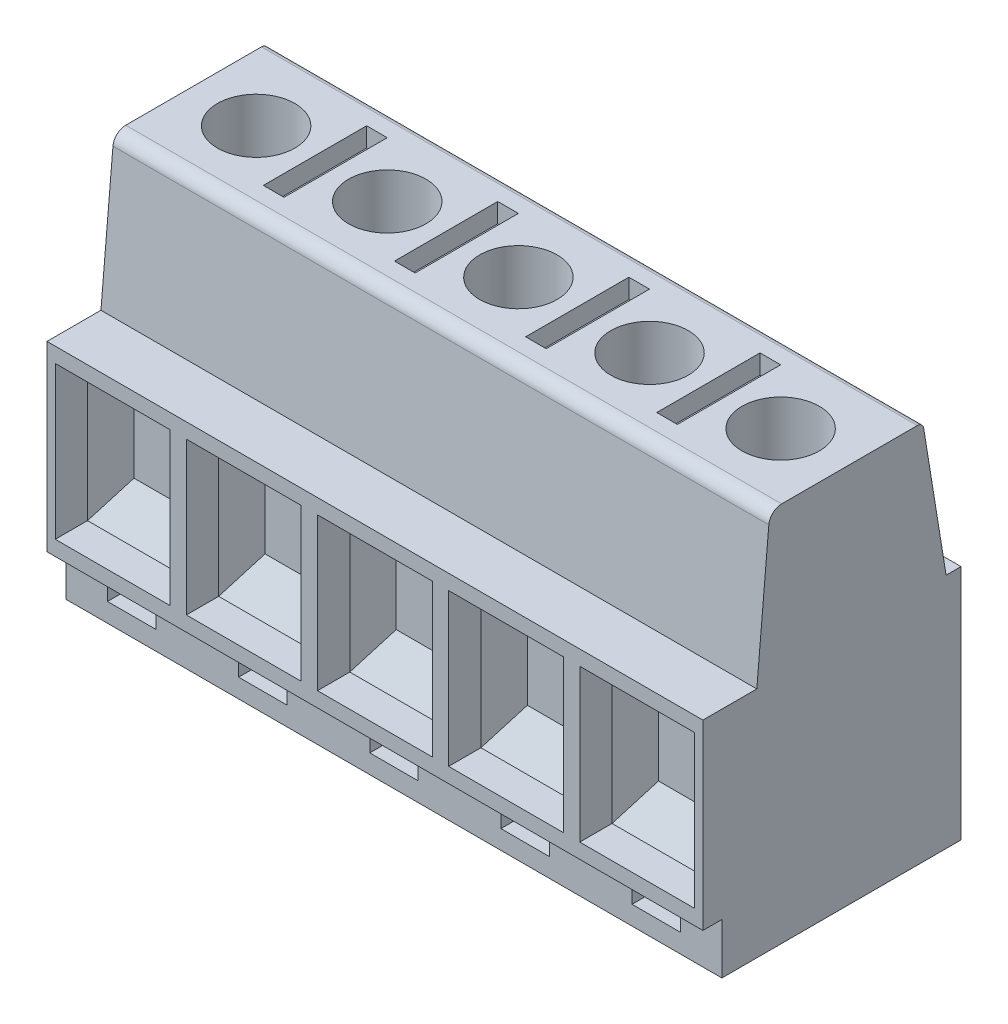
SolidWorks part; units mm, degrees
ref_plane "Front Plane" through (0, 0, 0) normal (0, 0, 1) x (1, 0, 0)
ref_plane "Top Plane" through (0, 0, 0) normal (0, 1, 0) x (1, 0, 0)
ref_plane "Right Plane" through (0, 0, 0) normal (1, 0, 0) x (0, 0, -1)
sketch "Sketch1" plane through (0, 0, 0) normal (1, 0, 0) x (0, 0, -1)
  line L0 (9.6447, 33.3244) -> (29.6447, 33.3244) construction
  line L1 (9.6692, 32.9692) -> (9.6692, 47.0868)
  line L2 (9.6692, 47.0868) -> (13.8475, 47.0868)
  line L3 (13.8475, 47.0868) -> (14.8593, 58.5419)
  line L4 (14.8593, 58.5419) -> (26.709, 58.5419)
  line L5 (26.709, 58.5419) -> (28.5149, 47.3865)
  line L6 (28.5149, 47.3865) -> (29.6692, 47.3865)
  line L7 (29.6692, 47.3865) -> (29.6692, 29.0419)
  line L8 (29.6692, 29.0419) -> (11.1423, 29.0419)
  line L9 (11.1423, 29.0419) -> (11.1423, 32.9692)
  line L10 (11.1423, 32.9692) -> (9.6692, 32.9692)
  line L11 (68.0457, 60.9618) -> (149.3457, 60.9618) construction
  line L12 (139.8559, 49.112) -> (148.7559, 49.112) construction
  line L13 (139.8559, 49.112) -> (139.8559, 37.312) construction
  line L14 (204.1416, 49.112) -> (206.6416, 49.112) construction
  line L15 (208.5587, 45.7504) -> (208.5587, 39.4578) construction
  line L16 (208.5587, 42.6041) -> (206.6416, 42.6041) construction
  line L17 (121.2763, 41.7533) -> (126.7736, 41.7533) construction
  line L18 (217.6919, 61.8593) -> (217.6919, 56.1569) construction
  line L19 (142.8406, 99.3741) -> (145.9297, 99.3741) construction
  line L20 (211.5813, 61.8593) -> (211.5813, 60.3558) construction
  line L21 (118.1896, 87.8673) -> (119.7969, 87.8673) construction
  line L22 (118.1896, 87.8673) -> (118.1896, 95.8627) construction
  line L23 (118.1896, 95.8627) -> (119.7969, 95.8627) construction
  line L24 (119.7969, 87.8673) -> (119.7969, 95.8627) construction
  line L25 (170.4098, 32.3653) -> (173.8098, 32.3653) construction
  line L26 (173.8098, 32.3653) -> (175.1098, 32.3653) construction
  line L27 (175.1098, 32.3653) -> (178.3098, 32.3653) construction
  line L28 (178.3098, 32.3653) -> (179.6098, 32.3653) construction
  line L29 (179.6098, 32.3653) -> (183.0098, 32.3653) construction
  line L30 (183.0098, 32.3653) -> (184.3098, 32.3653) construction
  line L31 (142.4541, 34.5696) -> (146.1866, 34.5696) construction
  line L32 (146.1866, 34.5696) -> (142.4541, 34.5696) construction
  line L33 (142.4541, 34.5696) -> (142.4541, 33.584) construction
  circle A0 centre (134.2519, 91.3377) radius 3.0186 construction
  dimension "D1" = 20
  dimension "D2" = 20
  dimension "D3" = 29.5
  dimension "D4" = 9.6692
  dimension "D5" = 11.1423
  dimension "D6" = 13.8475
  dimension "D7" = 14.8593
  dimension "D8" = 26.709
  dimension "D9" = 28.5149
  dimension "D10" = 29.0419
  dimension "D11" = 32.9692
  dimension "D12" = 33.3244
  dimension "D13" = 47.0868
  dimension "D14" = 47.3865
  dimension "D15" = 81.3
  dimension "D16" = 8.9
  dimension "D17" = 11.8
  dimension "D18" = 2.5
  dimension "D19" = 1.6073
  dimension "D20" = 7.9954
  dimension "D21" = 3.4
  dimension "D22" = 1.3
  dimension "D23" = 3.2
  dimension "D24" = 1.3
  dimension "D25" = 3.4
  dimension "D26" = 1.3
extrude "Boss-Extrude1" add sketch "Sketch1" along normal blind 10.16
sketch "Sketch2" plane through (0, 0, -9.6692) normal (0, 0, 1) x (1, 0, 0)
  line L0 (0, 47.0868) -> (0, 32.9692) construction
  line L1 (0.63, 34.128) -> (9.53, 34.128)
  line L2 (0.63, 34.128) -> (0.63, 45.928)
  line L3 (0.63, 45.928) -> (9.53, 45.928)
  line L4 (9.53, 34.128) -> (9.53, 45.928)
  line L5 (0.63, 34.128) -> (9.53, 45.928) construction
  line L6 (0.63, 45.928) -> (9.53, 34.128) construction
  line L7 (10.16, 47.0868) -> (0, 47.0868) construction
  point P0 (5.08, 40.028)
  point P5 (0, 0)
  point P8 (0, 40.028)
  point P9 (0, 0)
  point P12 (5.08, 47.0868)
  point P13 (9.3089, 45.6013)
  dimension "D1" = 8.9
  dimension "D2" = 11.8
extrude "Cut-Extrude1" cut sketch "Sketch2" against normal blind 2.5
sketch "Sketch3" plane through (0, 0, -12.1692) normal (0, 0, 1) x (1, 0, 0)
  line L4 (9.53, 34.128) -> (9.53, 45.928)
  line L5 (9.53, 45.928) -> (0.63, 45.928)
  line L6 (0.63, 45.928) -> (0.63, 34.128)
  line L7 (0.63, 34.128) -> (9.53, 34.128)
  line L8 (9.53, 34.128) -> (9.53, 45.928)
  line L9 (9.53, 45.928) -> (0.63, 45.928)
  line L10 (0.63, 45.928) -> (0.63, 34.128)
  line L11 (0.63, 34.128) -> (9.53, 34.128)
  dimension "D1" = 0
ref_plane "Plane1" through (0, 0, -14.0692) normal (0, 0, 1) x (1, 0, 0)
sketch "Sketch4" plane through (0, 0, -14.0692) normal (0, 0, 1) x (1, 0, 0)
  line L0 (9.53, 45.928) -> (0.63, 45.928) construction
  line L1 (2.33, 36.878) -> (7.83, 36.878)
  line L2 (2.33, 36.878) -> (2.33, 43.178)
  line L3 (2.33, 43.178) -> (7.83, 43.178)
  line L4 (7.83, 36.878) -> (7.83, 43.178)
  line L5 (2.33, 36.878) -> (7.83, 43.178) construction
  line L6 (2.33, 43.178) -> (7.83, 36.878) construction
  line L7 (0.63, 45.928) -> (0.63, 34.128) construction
  point P0 (5.08, 40.028)
  point P5 (0, 0)
  point P8 (5.08, 45.928)
  point P9 (0, 0)
  point P12 (0.63, 40.028)
  dimension "D1" = 6.3
  dimension "D2" = 5.5
loft "Cut-Loft1" cut profiles "Sketch3", "Sketch4" connector at (0.63, 45.928, -12.1692) connector at (2.33, 43.178, -14.0692)
sketch "Sketch5" plane through (0, 58.5419, 0) normal (0, 1, 0) x (1, 0, 0)
  line L0 (10.16, 26.709) -> (10.16, 14.8593) construction
  line L1 (10.16, 29.6692) -> (0, 29.6692) construction
  circle A0 centre (5.08, 20.7842) radius 3
  point P2 (0, 0)
  point P5 (10.16, 20.7842)
  point P6 (0, 0)
  point P9 (5.08, 29.6692)
  dimension "D1" = 6
extrude "Cut-Extrude2" cut sketch "Sketch5" against normal blind 5.7
sketch "Sketch7" plane through (0, 29.0419, 0) normal (0, -1, 0) x (1, 0, 0)
  line L0 (10.16, -11.1423) -> (0, -11.1423) construction
  line L1 (4.43, -27.5692) -> (5.73, -27.5692)
  line L2 (4.43, -27.5692) -> (4.43, -26.7692)
  line L3 (4.43, -26.7692) -> (5.73, -26.7692)
  line L4 (5.73, -27.5692) -> (5.73, -26.7692)
  line L5 (4.43, -27.5692) -> (5.73, -26.7692) construction
  line L6 (4.43, -26.7692) -> (5.73, -27.5692) construction
  line L7 (4.43, -17.4092) -> (5.73, -17.4092)
  line L8 (4.43, -17.4092) -> (4.43, -16.6092)
  line L9 (4.43, -16.6092) -> (5.73, -16.6092)
  line L10 (5.73, -17.4092) -> (5.73, -16.6092)
  line L11 (4.43, -17.4092) -> (5.73, -16.6092) construction
  line L12 (4.43, -16.6092) -> (5.73, -17.4092) construction
  line L13 (10.16, -29.6692) -> (0, -29.6692) construction
  point P0 (5.08, -27.1692)
  point P5 (5.08, -17.0092)
  point P10 (0, 0)
  point P13 (5.08, -11.1423)
  dimension "D1" = 1.3
  dimension "D2" = 0.8
  dimension "D3" = 2.5
  dimension "D4" = 10.16
extrude "Boss-Extrude2" add sketch "Sketch7" along normal blind 4.5
sketch "Sketch8" plane through (0, 0, -16.6092) normal (0, 0, 1) x (1, 0, 0)
  line L0 (4.43, 24.5419) -> (4.43, 29.0419) construction
  line L1 (5.73, 24.5419) -> (5.73, 29.0419) construction
  line L2 (5.73, 24.5419) -> (4.43, 24.5419) construction
  arc A0 (4.43, 25.1919) -> (5.73, 25.1919) centre (5.08, 25.1919) ccw
  point P3 (5.08, 24.5419)
extrude "Cut-Extrude5" cut sketch "Sketch8" against normal through all flip side to cut
ref_plane "Plane2" through (0, 38.5279, -38.5279) normal (0, 0.7071, -0.7071) x (-1, 0, 0)
sketch "Sketch10" plane through (0, 38.5279, -38.5279) normal (0, 0.7071, -0.7071) x (-1, 0, 0)
  line L0 (-10.16, 12.528) -> (0, 12.528) construction
  circle A0 centre (-5.08, 12.528) radius 1.5
  dimension "D1" = 3
extrude "Cut-Extrude6" cut sketch "Sketch10" against normal blind 4.5 contours A0
sketch "Sketch13" plane through (0, 0, -11.1423) normal (0, 0, 1) x (1, 0, 0)
  line L0 (10.16, 32.9692) -> (10.16, 29.0419) construction
  line L1 (3.205, 30.5055) -> (6.955, 30.5055)
  line L2 (3.205, 30.5055) -> (3.205, 31.5055)
  line L3 (3.205, 31.5055) -> (6.955, 31.5055)
  line L4 (6.955, 30.5055) -> (6.955, 31.5055)
  line L5 (3.205, 30.5055) -> (6.955, 31.5055) construction
  line L6 (3.205, 31.5055) -> (6.955, 30.5055) construction
  line L7 (10.16, 32.9692) -> (0, 32.9692) construction
  point P0 (5.08, 31.0055)
  point P5 (0, 0)
  point P8 (10.16, 31.0055)
  point P9 (0, 0)
  point P12 (5.08, 32.9692)
  dimension "D1" = 3.75
  dimension "D2" = 1
extrude "Cut-Extrude8" cut sketch "Sketch13" against normal blind 3
fillet "Fillet3" radius 0.5 1 edges at (5.08, 58.5419, -26.709) type face fillet first side face at (5.08, 58.5419, -17.7842) second side face at (5.08, 51.2437, -27.8905)
fillet "Fillet4" radius 1 1 edges at (5.08, 58.5419, -14.8593) type face fillet first side face at (5.08, 58.5419, -17.7842) second side face at (5.08, 52.8143, -14.3534)
sketch "Sketch12" plane through (0, 29.0419, 0) normal (0, -1, 0) x (1, 0, 0)
  line L1 (-0.65, -15.8423) -> (0.65, -15.8423)
  line L2 (-0.65, -15.8423) -> (-0.65, -14.5423)
  line L3 (-0.65, -14.5423) -> (0.65, -14.5423)
  line L4 (0.65, -15.8423) -> (0.65, -14.5423)
  line L5 (-0.65, -15.8423) -> (0.65, -14.5423) construction
  line L6 (-0.65, -14.5423) -> (0.65, -15.8423) construction
  line L8 (-0.65, -20.3423) -> (0.65, -20.3423)
  line L9 (-0.65, -20.3423) -> (-0.65, -19.0423)
  line L10 (-0.65, -19.0423) -> (0.65, -19.0423)
  line L11 (0.65, -20.3423) -> (0.65, -19.0423)
  line L12 (-0.65, -20.3423) -> (0.65, -19.0423) construction
  line L13 (-0.65, -19.0423) -> (0.65, -20.3423) construction
  line L14 (-0.65, -25.0423) -> (0.65, -25.0423)
  line L15 (-0.65, -25.0423) -> (-0.65, -23.7423)
  line L16 (-0.65, -23.7423) -> (0.65, -23.7423)
  line L17 (0.65, -25.0423) -> (0.65, -23.7423)
  line L18 (-0.65, -25.0423) -> (0.65, -23.7423) construction
  line L19 (-0.65, -23.7423) -> (0.65, -25.0423) construction
  line L20 (10.16, -11.1423) -> (0, -11.1423) construction
  line L21 (0, -11.1423) -> (0, -29.6692) construction
  point P0 (0, -15.1923)
  point P5 (0, 0)
  point P6 (0, -15.1923)
  point P7 (0, -19.6923)
  point P12 (0, -24.3923)
  point P21 (0, 0)
  point P22 (0, 0)
  point P23 (0, -15.1923)
  point P24 (0, -19.6923)
  point P25 (0, -24.3923)
  dimension "D1" = 3.4
  dimension "D2" = 1.3
  dimension "D3" = 3.2
  dimension "D4" = 3.4
  dimension "D5" = 1.3
extrude "Boss-Extrude3" add sketch "Sketch12" along normal blind 0.5 separate body
sketch "Sketch14" plane through (10.16, 0, 0) normal (1, 0, 0) x (0, 0, -1)
  line L10 (26.2835, 58.5419) -> (15.7749, 58.5419)
  line L11 (14.7788, 57.6298) -> (13.8475, 47.0868)
  line L12 (13.8475, 47.0868) -> (9.6692, 47.0868)
  line L13 (9.6692, 47.0868) -> (9.6692, 32.9692)
  line L14 (9.6692, 32.9692) -> (11.1423, 32.9692)
  line L15 (11.1423, 32.9692) -> (11.1423, 29.0419)
  line L16 (11.1423, 29.0419) -> (29.6692, 29.0419)
  line L17 (29.6692, 29.0419) -> (29.6692, 47.3865)
  line L18 (29.6692, 47.3865) -> (28.5149, 47.3865)
  line L19 (28.5149, 47.3865) -> (26.777, 58.1218)
  line L21 (14.7788, 57.6298) -> (13.8475, 47.0868)
  line L22 (13.8475, 47.0868) -> (9.6692, 47.0868)
  line L23 (9.6692, 47.0868) -> (9.6692, 32.9692)
  line L24 (9.6692, 32.9692) -> (11.1423, 32.9692)
  line L25 (11.1423, 32.9692) -> (11.1423, 29.0419)
  line L26 (11.1423, 29.0419) -> (29.6692, 29.0419)
  line L27 (29.6692, 29.0419) -> (29.6692, 47.3865)
  line L28 (29.6692, 47.3865) -> (28.5149, 47.3865)
  line L29 (28.5149, 47.3865) -> (26.777, 58.1218)
  line L31 (26.2835, 58.5419) -> (15.7749, 58.5419)
  arc A3 (26.777, 58.1218) -> (26.2835, 58.5419) centre (26.2835, 58.0419) ccw
  arc A6 (26.777, 58.1218) -> (26.2835, 58.5419) centre (26.2835, 58.0419) ccw
  arc A8 (15.7749, 58.5419) -> (14.7788, 57.6298) centre (15.7749, 57.5419) ccw
  arc A9 (15.7749, 58.5419) -> (14.7788, 57.6298) centre (15.7749, 57.5419) ccw
  dimension "D1" = 0
extrude "Boss-Extrude4" add sketch "Sketch14" along normal blind 0.01
ref_plane "Plane3" through (0, 0, 0) normal (-1, 0, 0) x (0, 0, 1)
pattern_linear "LPattern8" count 5 spacing 10.16 along (-1, 0, 0) of "Boss-Extrude1", "Cut-Extrude1", "Cut-Loft1", "Cut-Extrude2", "Boss-Extrude2", "Cut-Extrude5", "Cut-Extrude6", "Cut-Extrude8", "Fillet3", "Fillet4"
sketch "Sketch11" plane through (0, 58.5419, 0) normal (0, 1, 0) x (1, 0, 0)
  line L1 (-0.8, 17.0641) -> (0.8, 17.0641)
  line L2 (-0.8, 17.0641) -> (-0.8, 25.0641)
  line L3 (-0.8, 25.0641) -> (0.8, 25.0641)
  line L4 (0.8, 17.0641) -> (0.8, 25.0641)
  line L5 (-0.8, 17.0641) -> (0.8, 25.0641) construction
  line L6 (-0.8, 25.0641) -> (0.8, 17.0641) construction
  line L8 (0, 55) -> (0, -55) construction
  point P0 (0, 21.0641)
  point P5 (1.8522, 20.6032)
  point P6 (1.6707, 20.773)
  point P7 (0, 0)
  point P8 (0, 0)
  point P12 (0, 0)
  point P13 (0.3317, 21.0641)
  point P16 (0, 0)
  dimension "D1" = 1.6
  dimension "D2" = 8
extrude "Cut-Extrude7" cut sketch "Sketch11" against normal blind 1.5
pattern_linear "LPattern9" count 4 spacing 10.16 along (-1, 0, 0) of "Boss-Extrude3", "Cut-Extrude7"
sketch "Sketch16" plane through (-40.64, 0, 0) normal (-1, 0, 0) x (0, 0, 1)
  line L10 (-13.8475, 47.0868) -> (-14.7788, 57.6298)
  line L11 (-15.7749, 58.5419) -> (-26.2835, 58.5419)
  line L12 (-26.777, 58.1218) -> (-28.5149, 47.3865)
  line L13 (-28.5149, 47.3865) -> (-29.6692, 47.3865)
  line L14 (-29.6692, 47.3865) -> (-29.6692, 29.0419)
  line L15 (-29.6692, 29.0419) -> (-11.1423, 29.0419)
  line L16 (-11.1423, 29.0419) -> (-11.1423, 32.9692)
  line L17 (-11.1423, 32.9692) -> (-9.6692, 32.9692)
  line L18 (-9.6692, 32.9692) -> (-9.6692, 47.0868)
  line L19 (-9.6692, 47.0868) -> (-13.8475, 47.0868)
  line L62 (-13.8475, 47.0868) -> (-14.7788, 57.6298)
  line L63 (-15.7749, 58.5419) -> (-26.2835, 58.5419)
  line L64 (-26.777, 58.1218) -> (-28.5149, 47.3865)
  line L65 (-28.5149, 47.3865) -> (-29.6692, 47.3865)
  line L66 (-29.6692, 47.3865) -> (-29.6692, 29.0419)
  line L67 (-29.6692, 29.0419) -> (-11.1423, 29.0419)
  line L68 (-11.1423, 29.0419) -> (-11.1423, 32.9692)
  line L69 (-11.1423, 32.9692) -> (-9.6692, 32.9692)
  line L70 (-9.6692, 32.9692) -> (-9.6692, 47.0868)
  line L71 (-9.6692, 47.0868) -> (-13.8475, 47.0868)
  arc A2 (-14.7788, 57.6298) -> (-15.7749, 58.5419) centre (-15.7749, 57.5419) ccw
  arc A8 (-26.2835, 58.5419) -> (-26.777, 58.1218) centre (-26.2835, 58.0419) ccw
  arc A14 (-14.7788, 57.6298) -> (-15.7749, 58.5419) centre (-15.7749, 57.5419) ccw
  arc A15 (-26.2835, 58.5419) -> (-26.777, 58.1218) centre (-26.2835, 58.0419) ccw
  dimension "D1" = 0
extrude "Boss-Extrude6" add sketch "Sketch16" along normal blind 0.01
